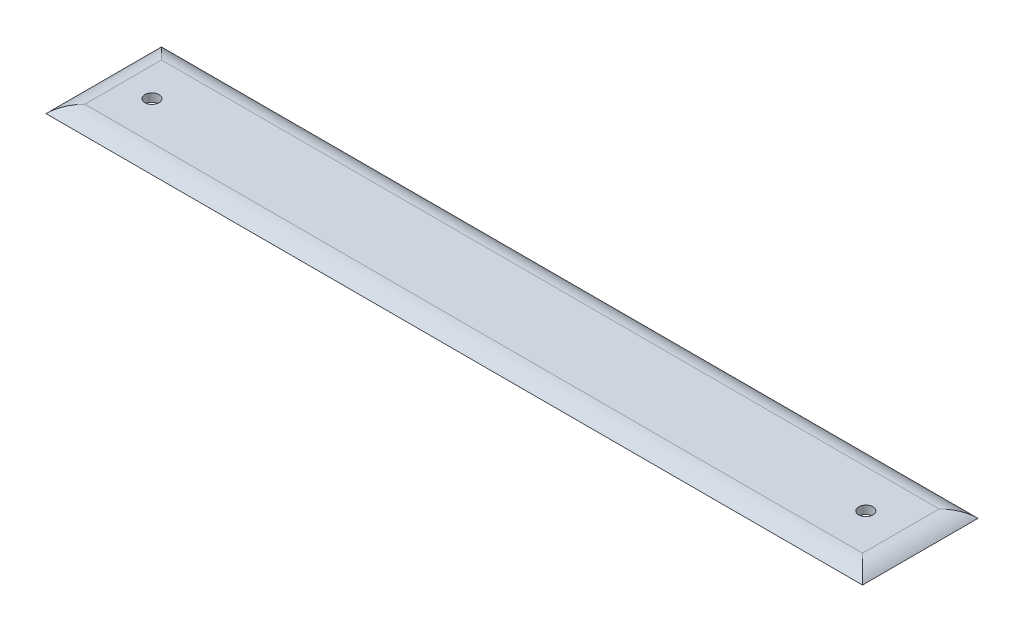
SolidWorks part; units mm, degrees
ref_plane "前视基准面" through (0, 0, 0) normal (0, 0, 1) x (1, 0, 0)
ref_plane "上视基准面" through (0, 0, 0) normal (0, 1, 0) x (1, 0, 0)
ref_plane "右视基准面" through (0, 0, 0) normal (1, 0, 0) x (0, 0, -1)
other "Configuration Table"
sketch "草图1" plane through (0, 0, 0) normal (0, 1, 0) x (1, 0, 0)
  line L1 (-129, 21.215) -> (129, 21.215)
  line L2 (-129, 21.215) -> (-129, -21.215)
  line L3 (-129, -21.215) -> (129, -21.215)
  line L4 (129, 21.215) -> (129, -21.215)
  line L5 (0, -21.215) -> (0, 21.215) construction
  line L6 (-129, 0) -> (129, 0) construction
  line L7 (-150, 21.215) -> (150, 21.215)
  line L8 (-150, 21.215) -> (-150, -21.215)
  line L9 (-150, -21.215) -> (150, -21.215)
  line L10 (150, 21.215) -> (150, -21.215)
  line L11 (0, -21.215) -> (0, 21.215) construction
  line L12 (-150, 0) -> (150, 0) construction
  circle A2 centre (130, 0) radius 2.6
  circle A3 centre (-132.3, 0) radius 2.6
  point P0 (0, 0)
  point P4 (0, 0)
  dimension "D4" = 5.2
  dimension "D5" = 20
  dimension "D6" = 5.2
  dimension "D1" = 258
  dimension "D2" = 42.43
  dimension "D3" = 300
  dimension "D7" = 17.7
extrude "凸台-拉伸1" add sketch "草图1" along normal blind 3 contours L2 L7 L8 L9 | L2 L3 L4 L1 | L4 L9 L10 L7 region at (-0.0651, 0, 0) region at (-139.6758, 0, 0) region at (139.6597, 0, 0)
fillet "圆角1" radius 10 4 edges at (150, 3, 0) (0, 3, 21.215) (-150, 3, 0) (0, 3, -21.215)
